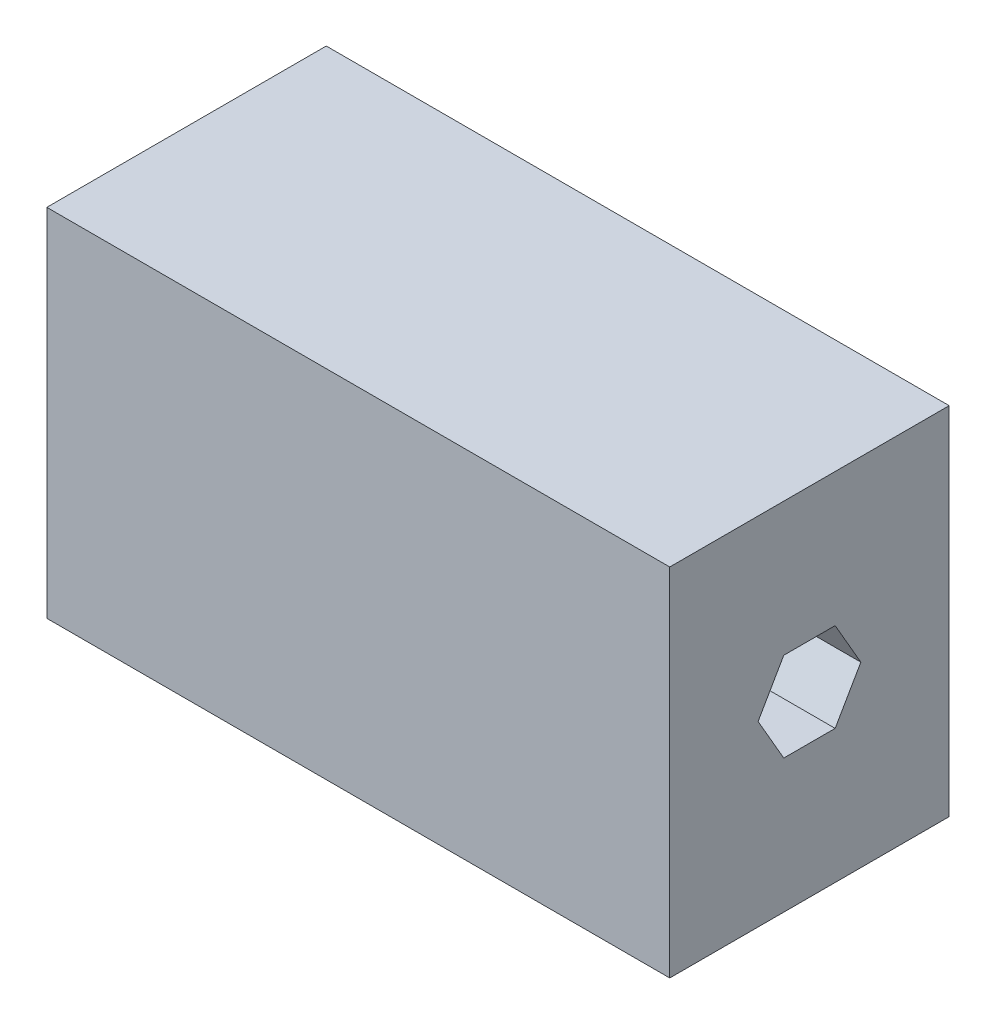
SolidWorks part; units mm, degrees
material "6061-T6 (SS)"
ref_plane "Front" through (0, 0, 0) normal (0, 0, 1) x (1, 0, 0)
ref_plane "Top" through (0, 0, 0) normal (0, 1, 0) x (1, 0, 0)
ref_plane "Right" through (0, 0, 0) normal (1, 0, 0) x (0, 0, -1)
sketch "Sketch1" plane through (0, 0, 0) normal (1, 0, 0) x (0, 0, -1)
  line L1 (19.939, -25.4) -> (-19.939, -25.4)
  line L2 (19.939, -25.4) -> (19.939, 25.4)
  line L3 (19.939, 25.4) -> (-19.939, 25.4)
  line L4 (-19.939, -25.4) -> (-19.939, 25.4)
  line L5 (19.939, -25.4) -> (-19.939, 25.4) construction
  line L6 (19.939, 25.4) -> (-19.939, -25.4) construction
  point P0 (0, 0)
  dimension "D1" = 50.8
  dimension "D2" = 39.878
extrude "Boss-Extrude1" add sketch "Sketch1" along normal blind 88.9
sketch "Sketch3" plane through (88.9, 0, 0) normal (1, 0, 0) x (0, 0, -1)
  line L1 (7.3323, 0) -> (3.6662, 6.35)
  line L2 (3.6662, 6.35) -> (-3.6662, 6.35)
  line L3 (-3.6662, 6.35) -> (-7.3323, 0)
  line L4 (-7.3323, 0) -> (-3.6662, -6.35)
  line L5 (-3.6662, -6.35) -> (3.6662, -6.35)
  line L6 (3.6662, -6.35) -> (7.3323, 0)
  circle A0 centre (0, 0) radius 6.35 construction
  dimension "D1" = 12.7
extrude "Cut-Extrude2" cut sketch "Sketch3" against normal through all
ref_axis "Axis1" through (-80.9, 0, 0) along (1, 0, 0)
